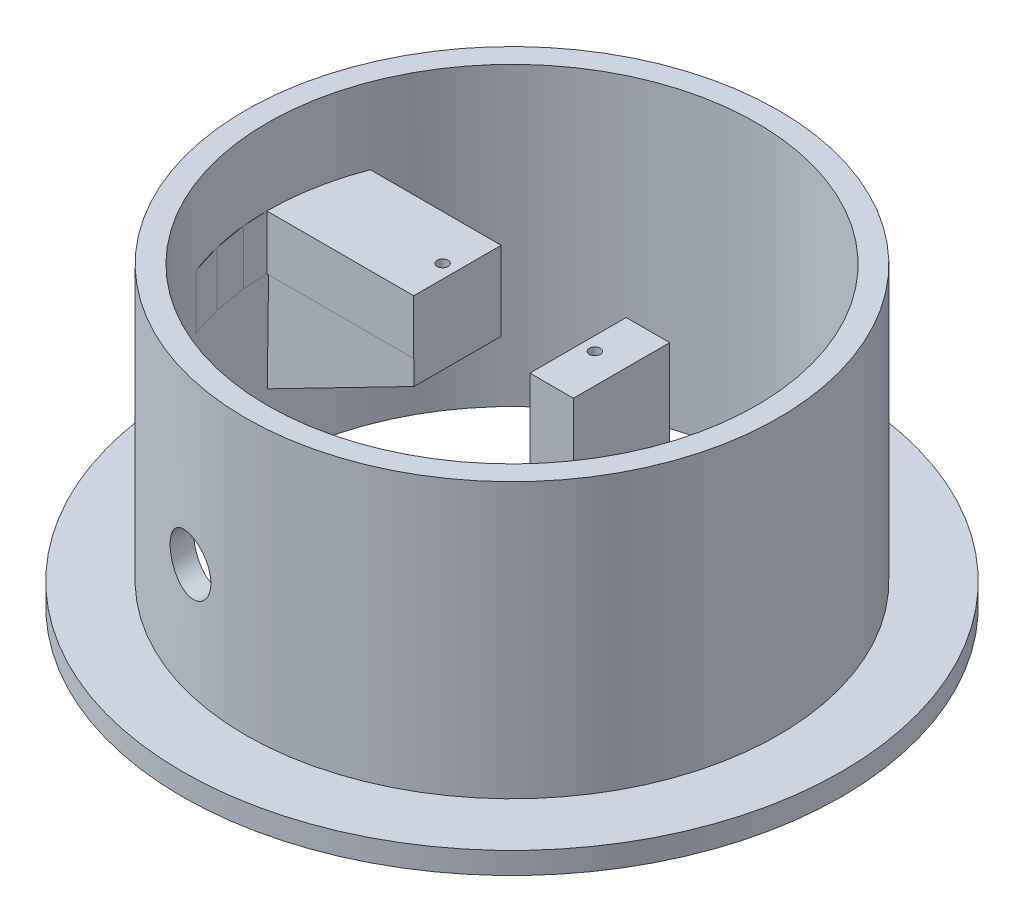
SolidWorks part; units mm, degrees
ref_plane "Front Plane" through (0, 0, 0) normal (0, 0, 1) x (1, 0, 0)
ref_plane "Top Plane" through (0, 0, 0) normal (0, 1, 0) x (1, 0, 0)
ref_plane "Right Plane" through (0, 0, 0) normal (1, 0, 0) x (0, 0, -1)
sketch "Sketch1" plane through (0, 0, 0) normal (0, 1, 0) x (1, 0, 0)
  circle A0 centre (0, 0) radius 60.625
  circle A1 centre (0, 0) radius 45
  dimension "D1" = 121.25
  dimension "D2" = 90
extrude "Boss-Extrude1" add sketch "Sketch1" along normal blind 4
sketch "Sketch2" plane through (0, 4, 0) normal (0, 1, 0) x (1, 0, 0)
  circle A0 centre (0, 0) radius 45 construction
  circle A1 centre (0, 0) radius 45
  circle A2 centre (0, 0) radius 49
  dimension "D1" = 4
extrude "Boss-Extrude2" add sketch "Sketch2" along normal blind 50.5
ref_plane "Plane1" through (0, 34.5, 0) normal (0, 1, 0) x (1, 0, 0)
sketch "Sketch4" plane through (0, 0, 0) normal (0, 0, 1) x (1, 0, 0)
  line L0 (-60.625, 0) -> (60.625, 0) construction
  line L1 (5, 40.5) -> (13, 40.5)
  line L2 (5, 40.5) -> (5, 0)
  line L3 (5, 0) -> (13, 0)
  line L4 (13, 40.5) -> (13, 0)
  line L5 (49, 54.5) -> (-49, 54.5) construction
  line L6 (-45, 54.5) -> (-45, 4)
  line L7 (-18, 40.5) -> (-45, 40.5)
  line L8 (-18, 40.5) -> (-18, 30.5)
  line L9 (-18, 30.5) -> (-45, 30.5)
  line L10 (-45, 40.5) -> (-45, 30.5)
  line L11 (60.625, 4) -> (-60.625, 4) construction
  line L12 (-18, 30.5) -> (-45, 3.5)
  dimension "D1" = 5
  dimension "D2" = 8
  dimension "D3" = 14
  dimension "D4" = 23
  dimension "D5" = 27
  dimension "D6" = 10
  dimension "D7" = 45
  dimension "D8" = 14
extrude "Boss-Extrude4" add sketch "Sketch4" along normal mid plane 32 contours L9 L8 L7 L6 | L12 L9 L6 | L1 L4 L3 L2 region at (-31.5, 35.5, 0)
sketch "Sketch5" plane through (0, 0, 0.8324) normal (0, -1, 0) x (1, 0, 0)
  line L0 (0.9227, 14.5796) -> (36.1058, 30.1379)
  line L1 (0.9227, -16.0291) -> (36.6512, -32.9046)
  line L2 (0.9227, 14.5796) -> (0.9227, -16.0291)
  arc A1 (36.6512, -32.9046) -> (36.1058, 30.1379) centre (-2.8733, -1.7229) ccw
extrude "Boss-Extrude5" add sketch "Sketch5" against normal up to surface (4 mm away) contours L0 A1 L1 L2 up to face at (0, 4, 60.625)
sketch "Sketch6" plane through (0, 0, 0) normal (0, 0, 1) x (1, 0, 0)
  circle A0 centre (-11.8474, 24.4856) radius 5
extrude "Cut-Extrude2" cut sketch "Sketch6" along normal blind 52 contours A0
sketch "Sketch7" plane through (0, 40.5, 0) normal (0, 1, 0) x (1, 0, 0)
  line L0 (-18, -16) -> (-18, 16) construction
  line L1 (5, -16) -> (5, 16) construction
  circle A0 centre (-20.5, 7.7399) radius 1
  circle A1 centre (7.5, 7.7399) radius 1
  dimension "D1" = 2.5
  dimension "D2" = 2.5
extrude "Cut-Extrude3" cut sketch "Sketch7" against normal blind 4.5
sketch "Sketch8" plane through (0, 40.5, 0.701) normal (0, 1, 0) x (1, 0, 0)
  line L1 (5, -1) -> (13, -1)
  line L2 (5, -1) -> (5, -16)
  line L3 (5, -16) -> (13, -16)
  line L4 (13, -1) -> (13, -16)
  dimension "D1" = 8
  dimension "D2" = 15
sketch "Sketch9" plane through (0, 40.5, 0.701) normal (0, 1, 0) x (1, 0, 0)
  line L1 (-41.34, 0.6311) -> (-16.34, 0.6311)
  line L2 (-41.34, 0.6311) -> (-41.34, -16.5689)
  line L3 (-41.34, -16.5689) -> (-16.34, -16.5689)
  line L4 (-16.34, 0.6311) -> (-16.34, -16.5689)
  dimension "D1" = 25
  dimension "D2" = 17.2
extrude "Cut-Extrude5" cut sketch "Sketch9" against normal blind 35
sketch "Sketch11" plane through (0, 4, 0) normal (0, 1, 0) x (1, 0, 0)
  line L0 (16.2655, 12.7324) -> (16.2655, -6.5497)
  line L1 (16.2655, -6.5497) -> (5.715, -6.5497)
  line L2 (5.715, -6.5497) -> (5.715, -11.643)
  line L3 (5.715, -11.643) -> (30.818, -22.5574)
  line L4 (16.2655, 12.7324) -> (32.152, 20.615)
  arc A0 (32.152, 20.615) -> (30.818, -22.5574) centre (5.8984, -0.1806) cw
extrude "Cut-Extrude6" cut sketch "Sketch11" against normal through all
extrude "Cut-Extrude7" cut sketch "Sketch8" against normal blind 36.5
sketch "Sketch12" plane through (0, 40.5, 0) normal (0, 1, 0) x (1, 0, 0)
  line L0 (-41.34, -0.0699) -> (-41.34, -16)
  line L1 (-41.34, -16) -> (-42.0595, -16)
  line L2 (-41.34, -16) -> (-42.0595, -16) construction
  line L3 (-42.0595, -16) -> (-43.7701, -10.449)
  line L4 (-43.7701, -10.449) -> (-44.7608, -4.6338)
  line L5 (-44.7608, -4.6338) -> (-44.9999, -0.0699)
  line L6 (-44.9999, -0.0699) -> (-41.34, -0.0699)
  circle A0 centre (0, 0) radius 45 construction
  arc A1 (-42.0595, 16) -> (-42.0595, -16) centre (0, 0) ccw construction
split "Split1" trim tools "Sketch12" bodies to split 135 resulting bodies 136 137
delete or keep bodies "Body-Delete/Keep 1" type delete bodies bodies 136
sketch "Sketch13" plane through (0, 0, 0) normal (0, 0, 1) x (1, 0, 0)
  line L0 (-44.7608, 30.5) -> (-18, 30.5)
  line L1 (-18, 30.5) -> (-18, 26.0152)
  line L2 (-18, 26.0152) -> (-45, 12.1404)
  line L3 (-45, 30.5) -> (-45, 0) construction
  line L4 (-45, 12.1404) -> (-44.7608, 30.5)
extrude "Boss-Extrude6" add sketch "Sketch13" against normal blind 16
